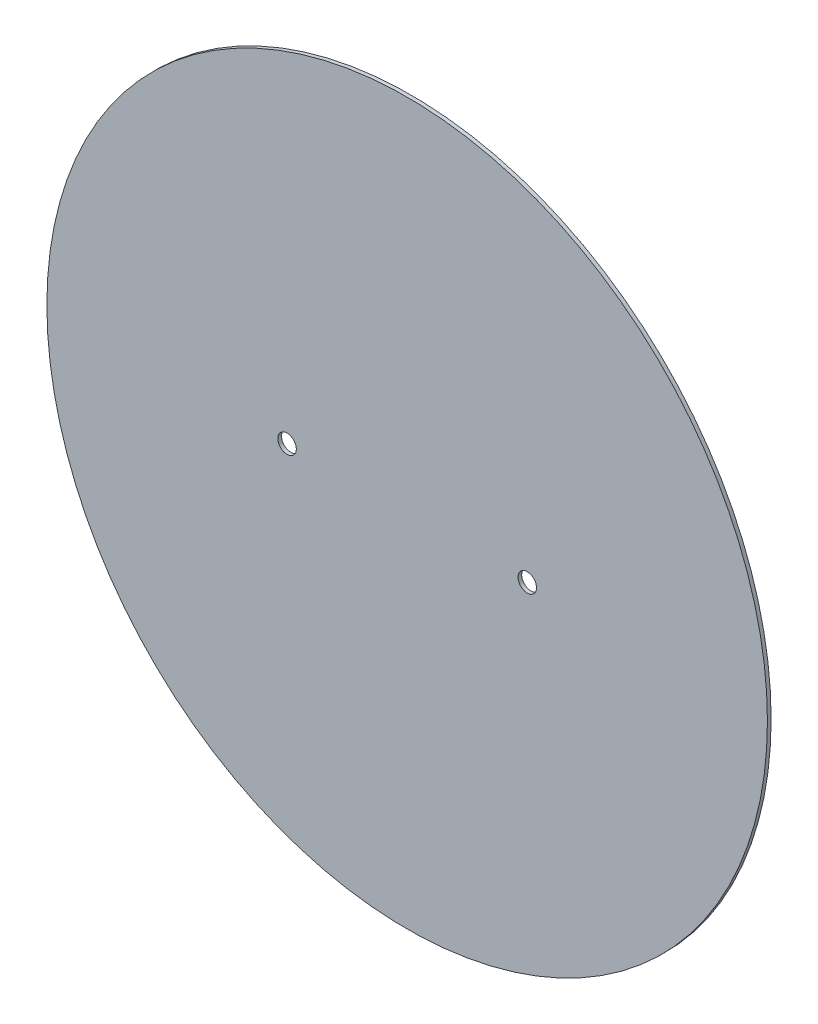
SolidWorks part; units mm, degrees
material "Aço galvanizado"
ref_plane "Plano frontal" through (0, 0, 0) normal (0, 0, 1) x (1, 0, 0)
ref_plane "Plano superior" through (0, 0, 0) normal (0, 1, 0) x (1, 0, 0)
ref_plane "Plano direito" through (0, 0, 0) normal (1, 0, 0) x (0, 0, -1)
sketch "Esboço1" plane through (0, 0, 0) normal (0, 0, 1) x (1, 0, 0)
  circle A0 centre (0, 0) radius 97.5
  dimension "D1" = 195
base flange "Flange-base1" sketch "Esboço1" thickness 1 reverse thickness direction no parameters "D1"=1.1
sketch "Esboço6" plane through (0, 0, -1) normal (0, 0, -1) x (-1, 0, 0)
  circle A0 centre (-32.5, 0) radius 2.5
  circle A1 centre (32.5, 0) radius 2.5
  point P0 (0, 0)
  point P13 (0, 0)
  dimension "D2" = 5
  dimension "D3" = 32.5
  dimension "D1" = 2
extrude "Corte-extrusão1" cut sketch "Esboço6" against normal through all normal cut yes
sketch "Curva-Linhas1" [suppressed] plane through (0, 0, 0) normal (0, 1, 0) x (1, 0, 0)
sketch "Caixa delimitadora1" [suppressed] plane through (0, 0, 0) normal (0, 1, 0) x (1, 0, 0)
sheet metal parameters "Chapa metálica1" thickness 1 parameters "D1"=1.1
flat pattern "Padrão-Plano1" [suppressed]
sketch "Curva-Linhas2" plane through (0, 0, 0) normal (0, 1, 0) x (1, 0, 0)
sketch3d "Caixa delimitadora2" [suppressed]
  line L0 (-85.1099, 85.36, 0) -> (-85.3599, -85.11, 0) construction
  line L1 (85.3599, 85.11, 0) -> (85.1099, -85.36, 0) construction
  line L2 (-85.1099, 85.36, 0) -> (85.3599, 85.11, 0) construction
  line L3 (-85.3599, -85.11, 0) -> (85.1099, -85.36, 0) construction
sheet metal parameters "Chapa metálica2" thickness 1 parameters "D1"=1.1
flat pattern "Padrão-Plano1"
sketch "Curva-Linhas2" plane through (0, 0, 0) normal (0, 1, 0) x (1, 0, 0)
sketch3d "Caixa delimitadora2" [suppressed]
  line L0 (97.3748, 97.6249, 0) -> (97.6248, -97.3749, 0) construction
  line L1 (-97.6249, 97.3749, 0) -> (-97.3749, -97.6249, 0) construction
  line L2 (97.3748, 97.6249, 0) -> (-97.6249, 97.3749, 0) construction
  line L3 (97.6248, -97.3749, 0) -> (-97.3749, -97.6249, 0) construction
